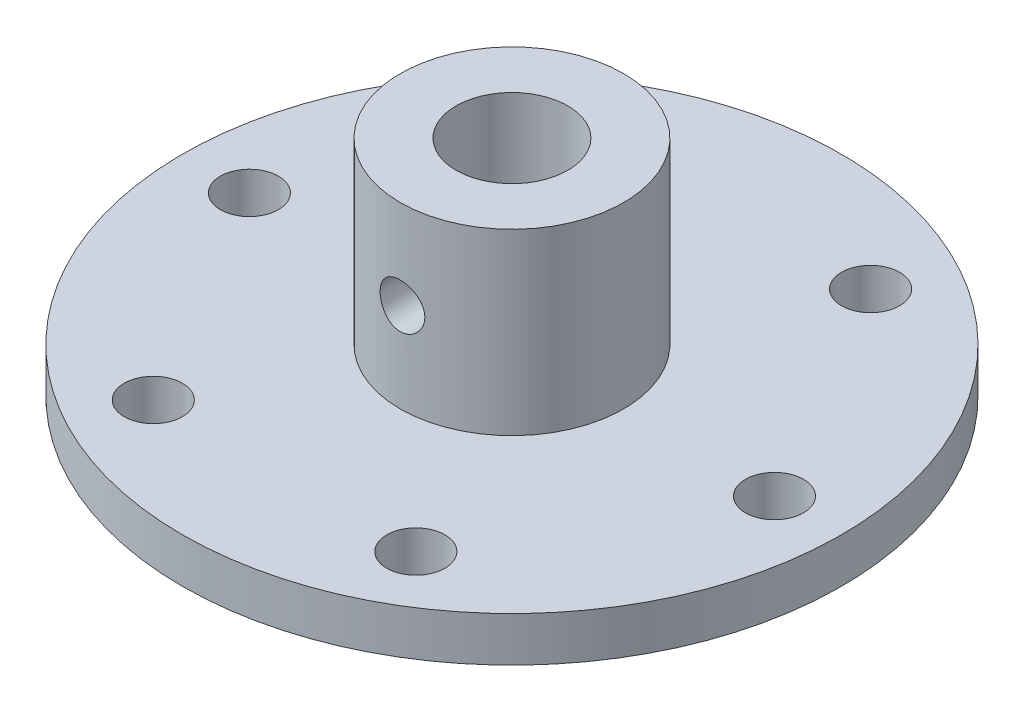
SolidWorks part; units mm, degrees
ref_plane "Front Plane" through (0, 0, 0) normal (0, 0, 1) x (1, 0, 0)
ref_plane "Top Plane" through (0, 0, 0) normal (0, 1, 0) x (1, 0, 0)
ref_plane "Right Plane" through (0, 0, 0) normal (1, 0, 0) x (0, 0, -1)
sketch "Sketch1" plane through (0, 0, 0) normal (0, 1, 0) x (1, 0, 0)
  circle A0 centre (0, 0) radius 29.5
  circle A1 centre (0, 0) radius 5
  circle A2 centre (0, 0) radius 10
  circle A3 centre (0, 0) radius 23.5 construction
  circle A4 centre (23.5, 0) radius 2.6
  circle A5 centre (11.75, -20.3516) radius 2.6
  circle A6 centre (-11.75, -20.3516) radius 2.6
  circle A7 centre (-23.5, 0) radius 2.6
  circle A8 centre (-11.75, 20.3516) radius 2.6
  circle A9 centre (11.75, 20.3516) radius 2.6
  point P20 (0, 0)
  dimension "D1" = 59
  dimension "D2" = 47
  dimension "D3" = 20
  dimension "D4" = 10
  dimension "D5" = 5.2
  dimension "D6" = 6
extrude "Boss-Extrude1" add sketch "Sketch1" along normal blind 4 contours A0 A2 | A2 A1 region at (-28.6656, 0, 0) region at (-9.7172, 0, 0)
extrude "Boss-Extrude2" add sketch "Sketch1<3>" along normal blind 20 contours A2 A1 region at (-9.7172, 0, 0)
sketch "Sketch1<3>" plane through (0, 0, 0) normal (0, 1, 0) x (1, 0, 0) same geometry as "Sketch1"
sketch "Sketch2" plane through (0, 0, 0) normal (0, 0, 1) x (1, 0, 0)
  line L0 (0, 20) -> (0, 4) construction
  line L2 (5, 20) -> (-5, 20) construction
  line L3 (29.5, 4) -> (-29.5, 4) construction
  circle A0 centre (0, 12) radius 2
  point P9 (0, 12)
  dimension "D1" = 4
extrude "Cut-Extrude1" cut sketch "Sketch2" against normal through all both and the other way through all
